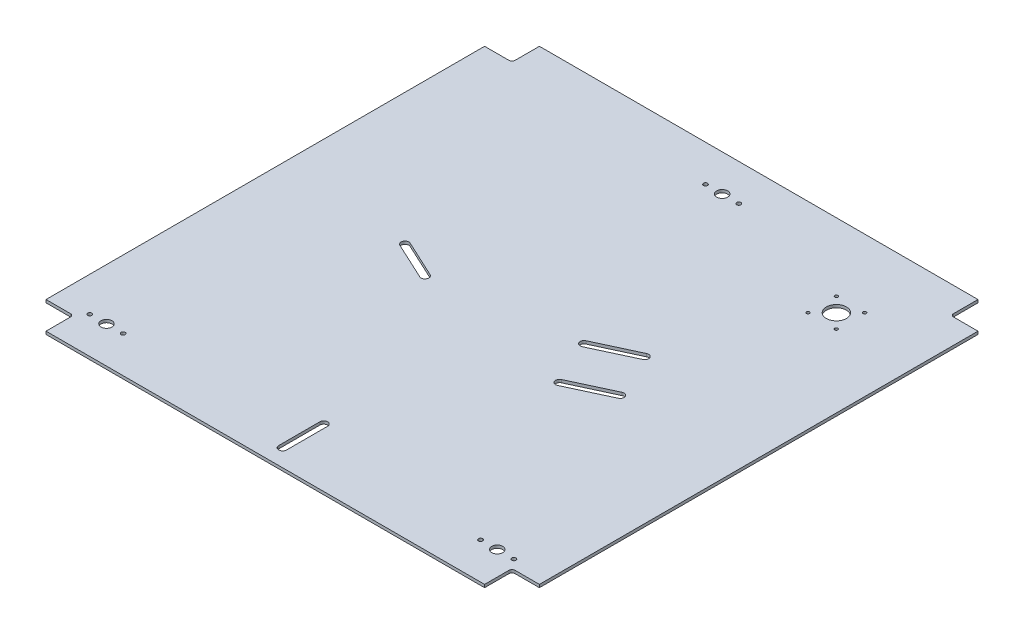
SolidWorks part; units mm, degrees
ref_plane "Front Plane" through (0, 0, 0) normal (0, 0, 1) x (1, 0, 0)
ref_plane "Top Plane" through (0, 0, 0) normal (0, 1, 0) x (1, 0, 0)
ref_plane "Right Plane" through (0, 0, 0) normal (1, 0, 0) x (0, 0, -1)
sketch "Sketch2" plane through (0, 0, 0) normal (0, 1, 0) x (1, 0, 0)
  line L0 (270, 0) -> (270, 540) construction
  line L1 (0, 0) -> (540, 0)
  line L2 (0, 0) -> (0, 540)
  line L3 (0, 540) -> (540, 540)
  line L4 (540, 0) -> (540, 540)
  line L5 (270, 500) -> (540, 500) construction
  circle A0 centre (56.175, 40) radius 6
  circle A1 centre (483.825, 40) radius 6
  circle A2 centre (270, 500) radius 6
  circle A3 centre (445, 450) radius 11
  dimension "D5" = 12
  dimension "D7" = 22
  dimension "D1" = 540
  dimension "D2" = 540
  dimension "D3" = 40
  dimension "D4" = 427.65
  dimension "D6" = 40
  dimension "D8" = 175
  dimension "D9" = 100
extrude "Boss-Extrude1" add sketch "Sketch2" along normal blind 3.175
chamfer "Chamfer1" [suppressed] distance 75 angle 45
hole_wizard "M4 Clearance Hole1" positions "3DSketch1" profile "Sketch3" hole size "M4" standard "ANSI Metric" end condition through all
sketch3d "3DSketch1"
  line L0 (56.175, 3.175, -40) -> (74.425, 3.175, -40) construction
  line L1 (56.175, 3.175, -40) -> (56.175, 0, -40) construction
  line L2 (56.175, 3.175, -40) -> (37.925, 3.175, -40) construction
  line L3 (483.825, 3.175, -40) -> (465.575, 3.175, -40) construction
  line L4 (483.825, 3.175, -40) -> (483.825, 0, -40) construction
  line L5 (483.825, 3.175, -40) -> (502.075, 3.175, -40) construction
  line L6 (270, 3.175, -500) -> (251.75, 3.175, -500) construction
  line L7 (270, 3.175, -500) -> (270, 0, -500) construction
  line L8 (270, 3.175, -500) -> (288.25, 3.175, -500) construction
  point P2 (74.425, 3.175, -40)
  point P4 (37.925, 3.175, -40)
  point P31 (251.75, 3.175, -500)
  point P33 (288.25, 3.175, -500)
  point P38 (465.575, 3.175, -40)
  point P40 (502.075, 3.175, -40)
  dimension "D1" = 36.5
sketch "Sketch3" plane through (74.425, 3.175, -40) normal (1, 0, 0) x (0, 0, 1)
  line L0 (0, 0) -> (0, 3.175)
  line L1 (0, 3.175) -> (2.25, 3.175)
  line L2 (2.25, 3.175) -> (2.25, 0)
  line L5 (2.25, 0) -> (0, 0)
  line L11 (0, -6.35) -> (0, 107.95) construction
  dimension "Thru Hole Dia." = 4.5
  dimension "Thru Hole Depth" = 3.175
hole_wizard "M3 Clearance Hole10" positions "3DSketch2" profile "Sketch4" hole size "M3" standard "ANSI Metric" end condition through all
sketch3d "3DSketch2"
  line L0 (429.5, 3.175, -465.5) -> (429.5, 3.175, -434.5) construction
  line L1 (429.5, 3.175, -434.5) -> (460.5, 3.175, -434.5) construction
  line L2 (460.5, 3.175, -434.5) -> (460.5, 3.175, -465.5) construction
  line L3 (460.5, 3.175, -465.5) -> (429.5, 3.175, -465.5) construction
  line L9 (445, 3.175, -450) -> (445, 3.175, -465.5) construction
  line L10 (445, 3.175, -450) -> (445, 0, -450) construction
  line L11 (445, 3.175, -450) -> (460.5, 3.175, -450) construction
  point P0 (429.5, 3.175, -465.5)
  point P2 (460.5, 3.175, -465.5)
  point P4 (460.5, 3.175, -434.5)
  point P6 (429.5, 3.175, -434.5)
  dimension "D1" = 31
sketch "Sketch4" plane through (429.5, 3.175, -465.5) normal (1, 0, 0) x (0, 0, 1)
  line L0 (0, 0) -> (0, 3.175)
  line L1 (0, 3.175) -> (1.7, 3.175)
  line L2 (1.7, 3.175) -> (1.7, 0)
  line L5 (1.7, 0) -> (0, 0)
  line L11 (0, -6.35) -> (0, 107.95) construction
  dimension "Thru Hole Dia." = 3.4
  dimension "Thru Hole Depth" = 3.175
sketch "Sketch5" plane through (0, 3.175, 0) normal (0, 1, 0) x (1, 0, 0)
  line L1 (0, 0) -> (30, 0)
  line L2 (0, 0) -> (0, 30)
  line L3 (0, 30) -> (30, 30)
  line L4 (30, 0) -> (30, 30)
  line L5 (540, 0) -> (510, 0)
  line L6 (540, 0) -> (540, 30)
  line L7 (540, 30) -> (510, 30)
  line L8 (510, 0) -> (510, 30)
  line L9 (540, 540) -> (510, 540)
  line L10 (540, 540) -> (540, 510)
  line L11 (540, 510) -> (510, 510)
  line L12 (510, 540) -> (510, 510)
  line L13 (0, 540) -> (30, 540)
  line L14 (0, 540) -> (0, 510)
  line L15 (0, 510) -> (30, 510)
  line L16 (30, 540) -> (30, 510)
  dimension "D1" = 30
extrude "Cut-Extrude1" cut sketch "Sketch5" against normal through all
fillet "Fillet1" radius 3.175 4 edges at (30, 1.5875, -510) (510, 1.5875, -510) (510, 1.5875, -30) (30, 1.5875, -30)
ref_axis "Axis1" through (270, 3.175, -500) along (0, -1, 0)
ref_plane "Plane1" through (270, 0, 0) normal (1, 0, 0) x (0, 0, -1)
sketch "Sketch8"
  dimension "D1" = 22
  dimension "D2" = 20
  dimension "D3" = 8
sketch "Sketch6" plane through (0, 3.175, 0) normal (0, 1, 0) x (1, 0, 0)
  line L0 (56.175, 40) -> (270, 500) construction
  line L1 (270, 500) -> (483.825, 40) construction
  line L2 (501.3641, 328.7444) -> (376.5705, 270.7357) construction
  line L3 (379.8937, 307.4751) -> (334.5528, 286.399)
  line L4 (383.4766, 299.7671) -> (338.1357, 278.691)
  line L5 (336.3443, 282.545) -> (381.6852, 303.6211) construction
  line L6 (405.0081, 253.4467) -> (359.6672, 232.3705) construction
  line L7 (279.975, 504.6367) -> (374.884, 300.4597) construction
  line L9 (376.5705, 270.7357) -> (104.6815, 144.3517) construction
  line L12 (379.291, 272.0003) -> (399.241, 281.2738) construction
  line L14 (403.2166, 257.3006) -> (357.8757, 236.2245)
  line L15 (406.7996, 249.5927) -> (361.4587, 228.5166)
  arc A0 (334.5528, 286.399) -> (338.1357, 278.691) centre (336.3443, 282.545) ccw
  arc A1 (379.8937, 307.4751) -> (383.4766, 299.7671) centre (381.6852, 303.6211) cw
  arc A6 (406.7996, 249.5927) -> (403.2166, 257.3006) centre (405.0081, 253.4467) ccw
  arc A7 (361.4587, 228.5166) -> (357.8757, 236.2245) centre (359.6672, 232.3705) cw
  point P39 (376.9125, 270)
  dimension "D1" = 8.5
  dimension "D2" = 7.5
  dimension "D5" = 50
extrude "Cut-Extrude2" cut sketch "Sketch6" against normal through all
sketch "Sketch9" plane through (0, 3.175, 0) normal (0, 1, 0) x (1, 0, 0)
  line L0 (270, 29) -> (270, 220.3031) construction
  line L1 (56.175, 29) -> (483.825, 29) construction
  line L2 (274.25, 19) -> (274.25, 64)
  line L3 (265.75, 64) -> (265.75, 19)
  line L4 (144.0443, 278.852) -> (184.8511, 259.8835) construction
  line L7 (153.1125, 274.6367) -> (270, 220.3031) construction
  line L8 (260.025, 504.6367) -> (46.2, 44.6367) construction
  line L9 (186.6426, 263.7374) -> (145.8358, 282.7059)
  line L10 (183.0597, 256.0295) -> (142.2529, 274.998)
  line L11 (270, 64) -> (270, 19) construction
  arc A0 (274.25, 64) -> (265.75, 64) centre (270, 64) ccw
  arc A1 (265.75, 19) -> (274.25, 19) centre (270, 19) ccw
  arc A2 (357.8757, 236.2245) -> (361.4587, 228.5166) centre (359.6672, 232.3705) ccw construction
  arc A5 (183.0597, 256.0295) -> (186.6426, 263.7374) centre (184.8511, 259.8835) ccw
  arc A6 (145.8358, 282.7059) -> (142.2529, 274.998) centre (144.0443, 278.852) ccw
  dimension "D2" = 10
  dimension "D3" = 45
  dimension "D4" = 10
extrude "Cut-Extrude3" cut sketch "Sketch9" against normal through all
